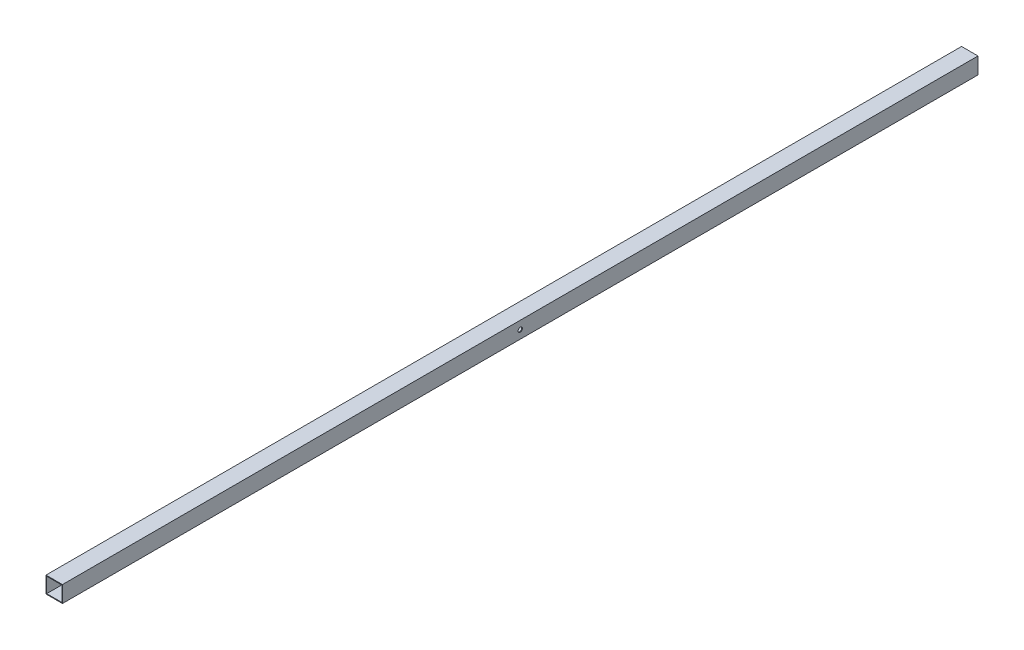
SolidWorks part; units mm, degrees
material "Plain Carbon Steel"
ref_plane "Front Plane" through (0, 0, 0) normal (0, 0, 1) x (1, 0, 0)
ref_plane "Top Plane" through (0, 0, 0) normal (0, 1, 0) x (1, 0, 0)
ref_plane "Right Plane" through (0, 0, 0) normal (1, 0, 0) x (0, 0, -1)
sketch "Sketch2" plane through (0, 0, 0) normal (0, 0, 1) x (1, 0, 0)
  line L0 (0, 19.05) -> (1.5875, 19.05) construction
  line L1 (0, 0) -> (38.1, 0)
  line L2 (0, 0) -> (0, 38.1)
  line L3 (0, 38.1) -> (38.1, 38.1)
  line L4 (38.1, 0) -> (38.1, 38.1)
  line L5 (1.5875, 1.5875) -> (36.5125, 1.5875)
  line L6 (1.5875, 1.5875) -> (1.5875, 36.5125)
  line L7 (1.5875, 36.5125) -> (36.5125, 36.5125)
  line L8 (36.5125, 1.5875) -> (36.5125, 36.5125)
  line L9 (19.05, 36.5125) -> (19.05, 38.1) construction
  line L10 (36.5125, 19.05) -> (38.1, 19.05) construction
  line L11 (19.05, 0) -> (19.05, 1.5875) construction
  dimension "D1" = 38.1
  dimension "D2" = 1.5875
  dimension "D3" = 38.1
extrude "Boss-Extrude1" add sketch "Sketch2" along normal blind 2120.9
hole_wizard "X (0.397) Diameter Hole1" positions "Sketch4" profile "Sketch3" hole size "X" standard "ANSI Inch" end condition through all
sketch "Sketch4" plane through (38.1, 0, 0) normal (1, 0, 0) x (0, 0, -1)
  line L0 (-2120.9, 0) -> (-2120.9, 38.1) construction
  line L1 (-2120.9, 0) -> (0, 0) construction
  point P0 (-1060.45, 19.05)
  dimension "D1" = 1060.45
  dimension "D2" = 19.05
sketch "Sketch3" plane through (38.1, 19.05, 1060.45) normal (0, 1, 0) x (0, 0, -1)
  line L0 (0, 0) -> (0, 38.1)
  line L1 (0, 38.1) -> (5.0419, 38.1)
  line L2 (5.0419, 38.1) -> (5.0419, 0)
  line L5 (5.0419, 0) -> (0, 0)
  line L11 (0, -6.35) -> (0, 107.95) construction
  dimension "Thru Hole Dia." = 10.0838
  dimension "Thru Hole Depth" = 38.1
